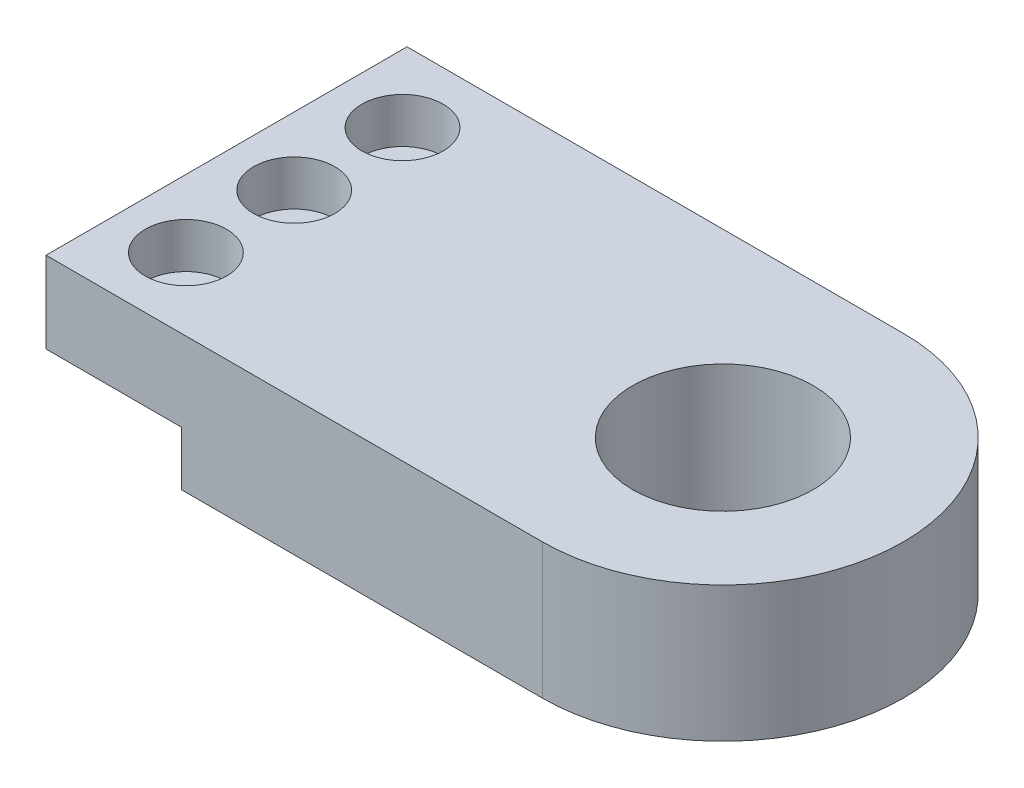
SolidWorks part; units mm, degrees
ref_plane "Front" through (0, 0, 0) normal (0, 0, 1) x (1, 0, 0)
ref_plane "Top" through (0, 0, 0) normal (0, 1, 0) x (1, 0, 0)
ref_plane "Right" through (0, 0, 0) normal (1, 0, 0) x (0, 0, -1)
sketch "草图1" plane through (0, 0, 0) normal (0, 1, 0) x (1, 0, 0)
  line L1 (0, 20) -> (-40, 20)
  line L2 (0, 20) -> (0, -20) construction
  line L3 (0, -20) -> (-40, -20)
  line L4 (-40, 20) -> (-40, -20)
  circle A0 centre (0, 0) radius 10
  arc A1 (0, 20) -> (0, -20) centre (0, 0) cw
  dimension "D1" = 20
  dimension "D3" = 20
  dimension "D2" = 40
extrude "凸台-拉伸1" add sketch "草图1" along normal blind 15
sketch "草图2" plane through (0, 0, 20) normal (0, 0, 1) x (1, 0, 0)
  line L1 (-40, 15) -> (-55, 15)
  line L2 (-40, 15) -> (-40, 6)
  line L3 (-40, 6) -> (-55, 6)
  line L4 (-55, 15) -> (-55, 6)
  dimension "D1" = 9
  dimension "D2" = 15
extrude "凸台-拉伸2" add sketch "草图2" against normal up to surface (40 mm away) up to face at (-20, 7.5, -20)
sketch "草图3" plane through (0, 15, 0) normal (0, 1, 0) x (1, 0, 0)
  line L0 (-47.5, 23.6613) -> (-47.5, -23.6613) construction
  line L1 (-57.8064, 0) -> (-25.0884, 0) construction
  line L2 (-55, 20) -> (-55, -20) construction
  circle A1 centre (-47.5, 12) radius 2.5
  circle A2 centre (-47.5, 12) radius 4.5
  circle A3 centre (-47.5, 0) radius 4.5
  circle A4 centre (-47.5, 0) radius 2.5
  circle A5 centre (-47.5, -12) radius 4.5
  circle A6 centre (-47.5, -12) radius 2.5
  dimension "D2" = 12
  dimension "D3" = 5
  dimension "D5" = 9
  dimension "D4" = 3
  dimension "D1" = 7.5
extrude "切除-拉伸1" cut sketch "草图3" against normal up to next contours A1 | A4 | A6 region at (-47.5, 15, -12) region at (-47.5, 15, 0) region at (-47.5, 15, 12)
extrude "切除-拉伸2" cut sketch "草图3<3>" against normal blind 5
sketch "草图3<3>" plane through (0, 15, 0) normal (0, 1, 0) x (1, 0, 0) same geometry as "草图3"
